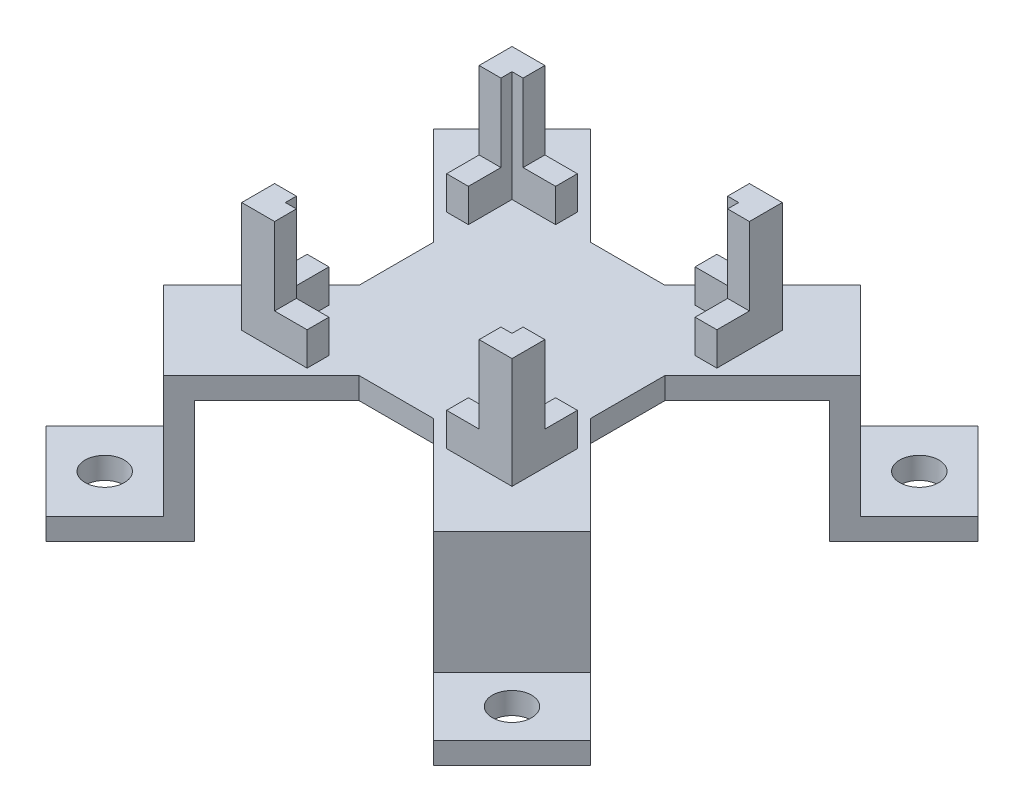
SolidWorks part; units mm, degrees
ref_plane "Front Plane" through (0, 0, 0) normal (0, 0, 1) x (1, 0, 0)
ref_plane "Top Plane" through (0, 0, 0) normal (0, 1, 0) x (1, 0, 0)
ref_plane "Right Plane" through (0, 0, 0) normal (1, 0, 0) x (0, 0, -1)
sketch "Sketch2" plane through (0, 0, 0) normal (0, 1, 0) x (1, 0, 0)
  line L0 (-48.9605, 31) -> (-26.5099, 8.5494)
  line L25 (-48.9605, 31) -> (-31, 48.9605)
  line L28 (-8.5494, -26.5099) -> (8.5494, -26.5099)
  line L29 (-26.5099, -8.5494) -> (-26.5099, 8.5494)
  line L30 (-8.5494, 26.5099) -> (8.5494, 26.5099)
  line L31 (26.5099, -8.5494) -> (26.5099, 8.5494)
  line L32 (-31, -31) -> (31, 31) construction
  line L33 (-31, 31) -> (31, -31) construction
  line L35 (-39.9803, 22.0197) -> (-22.0197, 39.9803) construction
  line L44 (-31, 48.9605) -> (-8.5494, 26.5099)
  line L47 (0, 31) -> (0, -31) construction
  line L49 (-31, 0) -> (31, 0) construction
  line L50 (31, 48.9605) -> (8.5494, 26.5099)
  line L51 (39.9803, 22.0197) -> (22.0197, 39.9803) construction
  line L52 (48.9605, 31) -> (31, 48.9605)
  line L53 (48.9605, 31) -> (26.5099, 8.5494)
  line L54 (48.9605, -31) -> (26.5099, -8.5494)
  line L55 (48.9605, -31) -> (31, -48.9605)
  line L56 (39.9803, -22.0197) -> (22.0197, -39.9803) construction
  line L57 (31, -48.9605) -> (8.5494, -26.5099)
  line L58 (-31, -48.9605) -> (-8.5494, -26.5099)
  line L59 (-39.9803, -22.0197) -> (-22.0197, -39.9803) construction
  line L60 (-48.9605, -31) -> (-31, -48.9605)
  line L61 (-48.9605, -31) -> (-26.5099, -8.5494)
  point P31 (0, 0)
  point P40 (-31, 31)
  dimension "D2" = 12.7
  dimension "D1" = 25.4
  dimension "D6" = 62
  dimension "D7" = 62
  dimension "D8" = 45
  dimension "D9" = 25.4
extrude "Boss-Extrude1" add sketch "Sketch2" along normal blind 5 contours L28 L57 L55 L54 L31 L53 L52 L50 L30 L44 L25 L0 L29 L61 L60 L58
sketch "Sketch3" plane through (0, 5, 0) normal (0, 1, 0) x (-1, 0, 0)
  line L0 (26, 31) -> (26, 16)
  line L5 (31, 16) -> (26, 16)
  line L15 (0, 0) -> (0, 31) construction
  line L40 (31, 31) -> (-31, 31) construction
  line L41 (31, 31) -> (31, -31) construction
  line L43 (31, -31) -> (-31, -31) construction
  line L92 (-31, 31) -> (-31, -31) construction
  line L97 (31, 31) -> (-31, -31) construction
  line L98 (31, -31) -> (-31, 31) construction
  line L99 (31, -31) -> (16, -31)
  line L100 (31, -31) -> (31, -26)
  line L101 (31, -26) -> (16, -26)
  line L102 (16, -31) -> (16, -26)
  line L103 (31, -31) -> (26, -31)
  line L104 (31, -31) -> (31, -16)
  line L105 (31, -16) -> (26, -16)
  line L106 (26, -31) -> (26, -16)
  line L107 (0, 0) -> (31, 0) construction
  line L108 (31, 31) -> (31, 16)
  line L109 (31, 31) -> (26, 31)
  line L110 (16, 31) -> (16, 26)
  line L111 (31, 26) -> (16, 26)
  line L112 (31, 31) -> (31, 26)
  line L113 (31, 31) -> (16, 31)
  line L114 (-31, 31) -> (-16, 31)
  line L115 (-31, 31) -> (-31, 26)
  line L116 (-31, 26) -> (-16, 26)
  line L117 (-16, 31) -> (-16, 26)
  line L118 (-31, 31) -> (-26, 31)
  line L119 (-31, 31) -> (-31, 16)
  line L120 (-26, -31) -> (-26, -16)
  line L121 (-31, -16) -> (-26, -16)
  line L122 (-31, -31) -> (-31, -16)
  line L123 (-31, -31) -> (-26, -31)
  line L124 (-16, -31) -> (-16, -26)
  line L125 (-31, -26) -> (-16, -26)
  line L126 (-31, -31) -> (-31, -26)
  line L127 (-31, -31) -> (-16, -31)
  line L128 (-31, 16) -> (-26, 16)
  line L129 (-26, 31) -> (-26, 16)
  point P1 (0, 0)
  line M131 (-26.5099, 8.5494) -> (-26.5099, -8.5494)
  dimension "D1" = 62
  dimension "D3" = 62
  dimension "D4" = 15
  dimension "D5" = 5
  dimension "D6" = 5
  dimension "D9" = 15
extrude "Boss-Extrude2" add sketch "Sketch3" along normal blind 7.62 contours L122 L125 L120 L121 M131 | L118 L129 L128 L119 | L114 L117 L116 L115 | L113 L110 L111 L112 | L109 L0 L5 L108 | L127 L124 L125 L126 | L100 L99 L102 L101 | L104 L103 L106 L105 region at (28.5, 5, -21)
sketch "Sketch4" plane through (0, 0, 0) normal (0, -1, 0) x (-1, 0, 0)
  line L21 (0, 0) -> (0, 26.5099) construction
  line L24 (8.5494, 26.5099) -> (-8.5494, 26.5099) construction
  line L42 (48.9605, -31) -> (45.425, -27.4645)
  line L43 (48.9605, -31) -> (26.5099, -8.5494) construction
  line L44 (45.425, -27.4645) -> (27.4645, -45.425)
  line L45 (31, -48.9605) -> (8.5494, -26.5099) construction
  line L46 (27.4645, -45.425) -> (31, -48.9605)
  line L47 (31, -48.9605) -> (48.9605, -31)
  line L48 (0, 0) -> (26.5099, 0) construction
  line L49 (26.5099, -8.5494) -> (26.5099, 8.5494) construction
  line L50 (31, 48.9605) -> (48.9605, 31)
  line L51 (27.4645, 45.425) -> (31, 48.9605)
  line L52 (45.425, 27.4645) -> (27.4645, 45.425)
  line L53 (48.9605, 31) -> (45.425, 27.4645)
  line L54 (-48.9605, 31) -> (-45.425, 27.4645)
  line L55 (-45.425, 27.4645) -> (-27.4645, 45.425)
  line L56 (-27.4645, 45.425) -> (-31, 48.9605)
  line L57 (-31, 48.9605) -> (-48.9605, 31)
  line L58 (-31, -48.9605) -> (-48.9605, -31)
  line L59 (-27.4645, -45.425) -> (-31, -48.9605)
  line L60 (-45.425, -27.4645) -> (-27.4645, -45.425)
  line L61 (-48.9605, -31) -> (-45.425, -27.4645)
  dimension "D2" = 5
extrude "Boss-Extrude3" add sketch "Sketch4" along normal blind 28 contours L54 L55 L56 L57 | L50 L53 L52 L51 | L47 L42 L44 L46 | L58 L61 L60 L59
sketch "Sketch5" plane through (104.0869, 0, 24.1264) normal (-0.7071, 0, 0.7071) x (0.7071, 0, 0.7071)
  line L0 (-77.9605, 5) -> (-77.9605, -28) construction
  line L10 (-103.3605, -28) -> (-77.9605, -28)
  line L11 (-103.3605, -28) -> (-103.3605, -23)
  line L12 (-103.3605, -23) -> (-77.9605, -23)
  line L13 (-77.9605, -28) -> (-77.9605, -23)
  dimension "D1" = 5
extrude "Boss-Extrude4" add sketch "Sketch5" against normal blind 19.05
sketch "Sketch6" plane through (32.4462, 0, -112.4067) normal (0.7071, 0, 0.7071) x (0.7071, 0, -0.7071)
  line L14 (-89.7264, 5) -> (-89.7264, -28) construction
  line L15 (-115.1264, -28) -> (-89.7264, -28)
  line L16 (-115.1264, -28) -> (-115.1264, -23)
  line L17 (-115.1264, -23) -> (-89.7264, -23)
  line L18 (-89.7264, -28) -> (-89.7264, -23)
  dimension "D1" = 5
extrude "Boss-Extrude5" add sketch "Sketch6" against normal blind 19.05
sketch "Sketch7" plane through (-39.9803, 0, 39.9803) normal (0.7071, 0, -0.7071) x (-0.7071, 0, -0.7071)
  line L10 (-12.7, -28) -> (12.7, -28)
  line L11 (-12.7, -28) -> (-12.7, -23)
  line L12 (-12.7, -23) -> (12.7, -23)
  line L13 (12.7, -28) -> (12.7, -23)
extrude "Boss-Extrude6" add sketch "Sketch7" against normal blind 19.05
sketch "Sketch8" plane through (39.9803, 0, 39.9803) normal (0.7071, 0, 0.7071) x (0.7071, 0, -0.7071)
  line L5 (-12.7, -28) -> (12.7, -28)
  line L6 (-12.7, -28) -> (-12.7, -23)
  line L7 (-12.7, -23) -> (12.7, -23)
  line L8 (12.7, -28) -> (12.7, -23)
extrude "Boss-Extrude7" add sketch "Sketch8" along normal blind 19.05
sketch "Sketch9" plane through (0, -23, 0) normal (0, 1, 0) x (1, 0, 0)
  line L0 (39.9803, 39.9803) -> (53.4506, 53.4506) construction
  line L3 (48.9605, 31) -> (31, 48.9605) construction
  line L6 (62.4309, 44.4704) -> (44.4704, 62.4309) construction
  line L12 (39.9803, -39.9803) -> (53.4506, -53.4506) construction
  line L13 (48.9605, -31) -> (31, -48.9605) construction
  line L14 (62.4309, -44.4704) -> (44.4704, -62.4309) construction
  line L15 (-39.9803, 39.9803) -> (-53.4506, 53.4506) construction
  line L16 (-31, 48.9605) -> (-48.9605, 31) construction
  line L17 (-44.4704, 62.4309) -> (-62.4309, 44.4704) construction
  line L18 (-39.9803, -39.9803) -> (-53.4506, -53.4506) construction
  line L19 (-48.9605, -31) -> (-31, -48.9605) construction
  line L20 (-62.4309, -44.4704) -> (-44.4704, -62.4309) construction
  circle A4 centre (46.7154, -46.7154) radius 4.5
  circle A5 centre (46.7154, 46.7154) radius 4.5
  circle A6 centre (-46.7154, 46.7154) radius 4.5
  circle A7 centre (-46.7154, -46.7154) radius 4.5
  circle A8 centre (-46.7154, -46.7154) radius 8 construction
  circle A9 centre (46.7154, -46.7154) radius 8 construction
  circle A10 centre (46.7154, 46.7154) radius 8 construction
  circle A11 centre (-46.7154, 46.7154) radius 8 construction
  dimension "D1" = 9
  dimension "D2" = 16
  dimension "D3" = 9
  dimension "D5" = 9
  dimension "D6" = 9
  dimension "D7" = 16
  dimension "D8" = 16
  dimension "D9" = 16
extrude "Cut-Extrude1" cut sketch "Sketch9" against normal blind 12.7
sketch "Sketch10" plane through (0, 5, 0) normal (0, 1, 0) x (1, 0, 0)
  line L0 (31, -31) -> (31, -16) construction
  line L21 (31, -31) -> (26, -31)
  line L26 (0, 0) -> (0, 26.5099) construction
  line L27 (31, -31) -> (31, -26)
  line L28 (31, -26) -> (26, -26)
  line L29 (-8.5494, 26.5099) -> (8.5494, 26.5099) construction
  line L30 (26, -31) -> (26, -26)
  line L31 (26, -26) -> (31, -26)
  line L56 (26, -26) -> (26, -23.46)
  line L65 (26, -23.46) -> (31, -23.46)
  line L70 (31, -26) -> (31, -23.46)
  line L79 (31, -31) -> (16, -31) construction
  line L84 (26, -26) -> (23.46, -26)
  line L93 (26, -26) -> (26, -31)
  line L112 (0, 0) -> (26.5099, 0) construction
  line L113 (26.5099, -8.5494) -> (26.5099, 8.5494) construction
  line L114 (26, -31) -> (23.46, -31)
  line L115 (23.46, -26) -> (23.46, -31)
  line L116 (23.46, 26) -> (23.46, 31)
  line L117 (26, 31) -> (23.46, 31)
  line L118 (26, 26) -> (26, 31)
  line L119 (26, 26) -> (23.46, 26)
  line L120 (31, 26) -> (31, 23.46)
  line L121 (26, 23.46) -> (31, 23.46)
  line L126 (26, 26) -> (26, 23.46)
  line L127 (26, 26) -> (31, 26)
  line L128 (26, 31) -> (26, 26)
  line L129 (31, 26) -> (26, 26)
  line L138 (31, 31) -> (31, 26)
  line L139 (31, 31) -> (26, 31)
  line L140 (31, -31) -> (26, -31)
  line L141 (31, -31) -> (31, -26)
  line L142 (31, -26) -> (26, -26)
  line L143 (26, -31) -> (26, -26)
  line L144 (26, -26) -> (31, -26)
  line L145 (26, -26) -> (26, -23.46)
  line L150 (26, -23.46) -> (31, -23.46)
  line L151 (31, -26) -> (31, -23.46)
  line L152 (26, -26) -> (23.46, -26)
  line L153 (26, -26) -> (26, -31)
  line L154 (26, -31) -> (23.46, -31)
  line L155 (23.46, -26) -> (23.46, -31)
  line L156 (23.46, 26) -> (23.46, 31)
  line L157 (26, 31) -> (23.46, 31)
  line L158 (26, 26) -> (26, 31)
  line L159 (26, 26) -> (23.46, 26)
  line L160 (31, 26) -> (31, 23.46)
  line L161 (26, 23.46) -> (31, 23.46)
  line L162 (26, 26) -> (26, 23.46)
  line L163 (26, 26) -> (31, 26)
  line L164 (26, 31) -> (26, 26)
  line L165 (31, 26) -> (26, 26)
  line L166 (31, 31) -> (31, 26)
  line L167 (31, 31) -> (26, 31)
  line L168 (-31, 31) -> (-26, 31)
  line L169 (-31, 31) -> (-31, 26)
  line L170 (-31, 26) -> (-26, 26)
  line L171 (-26, 31) -> (-26, 26)
  line L172 (-26, 26) -> (-31, 26)
  line L173 (-26, 26) -> (-26, 23.46)
  line L174 (-26, 23.46) -> (-31, 23.46)
  line L175 (-31, 26) -> (-31, 23.46)
  line L176 (-26, 26) -> (-23.46, 26)
  line L177 (-26, 26) -> (-26, 31)
  line L178 (-26, 31) -> (-23.46, 31)
  line L179 (-23.46, 26) -> (-23.46, 31)
  line L180 (-23.46, -26) -> (-23.46, -31)
  line L181 (-26, -31) -> (-23.46, -31)
  line L182 (-26, -26) -> (-26, -31)
  line L183 (-26, -26) -> (-23.46, -26)
  line L184 (-31, -26) -> (-31, -23.46)
  line L185 (-26, -23.46) -> (-31, -23.46)
  line L186 (-26, -26) -> (-26, -23.46)
  line L187 (-26, -26) -> (-31, -26)
  line L188 (-26, -31) -> (-26, -26)
  line L189 (-31, -26) -> (-26, -26)
  line L190 (-31, -31) -> (-31, -26)
  line L191 (-31, -31) -> (-26, -31)
  line L192 (-31, 31) -> (-26, 31)
  line L193 (-31, 31) -> (-31, 26)
  line L194 (-31, 26) -> (-26, 26)
  line L195 (-26, 31) -> (-26, 26)
  line L196 (-26, 26) -> (-31, 26)
  line L197 (-26, 26) -> (-26, 23.46)
  line L198 (-26, 23.46) -> (-31, 23.46)
  line L199 (-31, 26) -> (-31, 23.46)
  line L200 (-26, 26) -> (-23.46, 26)
  line L201 (-26, 26) -> (-26, 31)
  line L202 (-26, 31) -> (-23.46, 31)
  line L203 (-23.46, 26) -> (-23.46, 31)
  line L204 (-23.46, -26) -> (-23.46, -31)
  line L205 (-26, -31) -> (-23.46, -31)
  line L206 (-26, -26) -> (-26, -31)
  line L207 (-26, -26) -> (-23.46, -26)
  line L208 (-31, -26) -> (-31, -23.46)
  line L209 (-26, -23.46) -> (-31, -23.46)
  line L210 (-26, -26) -> (-26, -23.46)
  line L211 (-26, -26) -> (-31, -26)
  line L212 (-26, -31) -> (-26, -26)
  line L213 (-31, -26) -> (-26, -26)
  line L214 (-31, -31) -> (-31, -26)
  line L215 (-31, -31) -> (-26, -31)
  line M140 (26, 16) -> (26, 26)
  line M141 (26, 26) -> (16, 26)
  line M145 (-16, 26) -> (-26, 26)
  line M146 (-26, 26) -> (-26, 16)
  line M150 (-26, -16) -> (-26, -26)
  line M151 (-26, -26) -> (-16, -26)
  line M155 (16, -26) -> (26, -26)
  line M156 (26, -26) -> (26, -16)
  dimension "D2" = 2.54
  dimension "D3" = 2.54
extrude "Boss-Extrude8" add sketch "Sketch10" along normal blind 25.4 contours L118 L117 L116 M141 | L138 L139 L118 L127 | L127 L121 L120 M140 | L28 L70 L65 M156 | L30 L21 L27 L28 | L115 L114 L30 M155 | L187 L185 L184 M150 | L190 L191 L182 L187 | L182 L181 L180 M151 | L170 L175 L174 M146 | L171 L168 L169 L170 | L179 L178 L171 M145 region at (28.5, 5, 28.5) region at (24.73, 5, 28.5) region at (28.5, 5, 24.73) region at (24.73, 5, -28.5) region at (28.5, 5, -24.73) region at (28.5, 5, -28.5) region at (-28.5, 5, -28.5) region at (-24.73, 5, -28.5) region at (-28.5, 5, -24.73) region at (-24.73, 5, 28.5) region at (-28.5, 5, 24.73) region at (-28.5, 5, 28.5)
